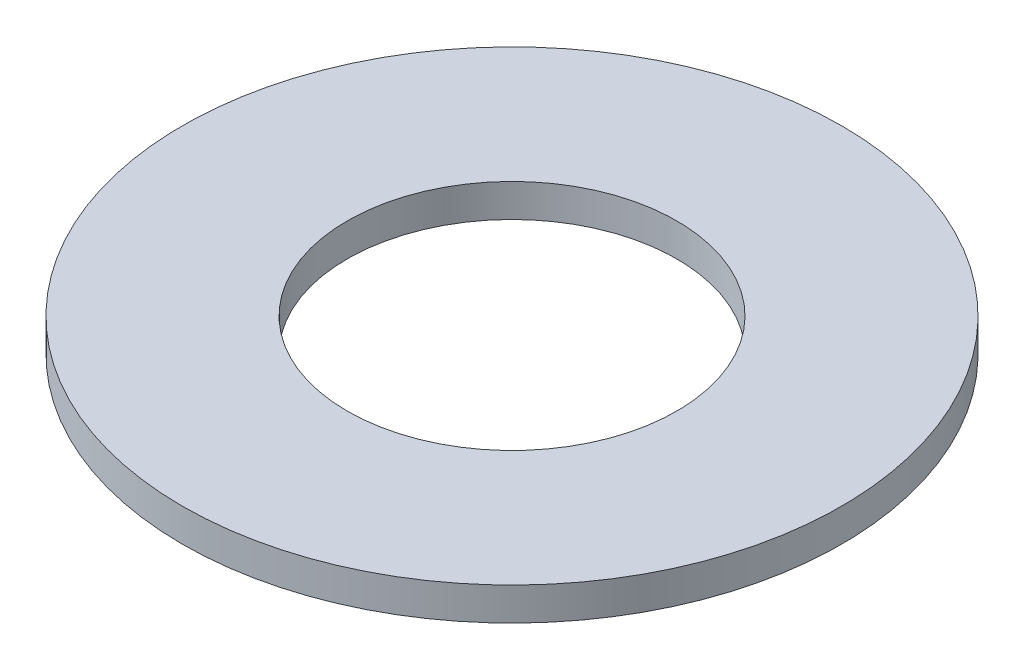
SolidWorks part; units mm, degrees
ref_plane "Front Plane" through (0, 0, 0) normal (0, 0, 1) x (1, 0, 0)
ref_plane "Top Plane" through (0, 0, 0) normal (0, 1, 0) x (1, 0, 0)
ref_plane "Right Plane" through (0, 0, 0) normal (1, 0, 0) x (0, 0, -1)
sketch "Sketch1" plane through (0, 0, 0) normal (0, 1, 0) x (1, 0, 0)
  circle A0 centre (0, 0) radius 90
  dimension "FLANGE_OD" = 180
extrude "Boss-Extrude1" add sketch "Sketch1" along normal blind 9
sketch "Sketch2" plane through (0, 0, 0) normal (0, 1, 0) x (1, 0, 0)
  circle A0 centre (0, 0) radius 45
  dimension "BORE_D" = 90
extrude "Cut-Extrude1" cut sketch "Sketch2" along normal through all
sketch "Sketch3" plane through (0, 9, 0) normal (0, 1, 0) x (1, 0, 0)
  circle A0 centre (0, 0) radius 39.0001 construction
  circle A1 centre (-39.0001, 0) radius 4.7806
  dimension "BOLT_D" = 9.5612
  dimension "BOLT_PCD" = 78.0001
extrude "Cut-Extrude2" cut sketch "Sketch3" against normal blind 7.9188 rebuild error yes
pattern_circular "CirPattern1" count 8 over 360 rebuild error yes
